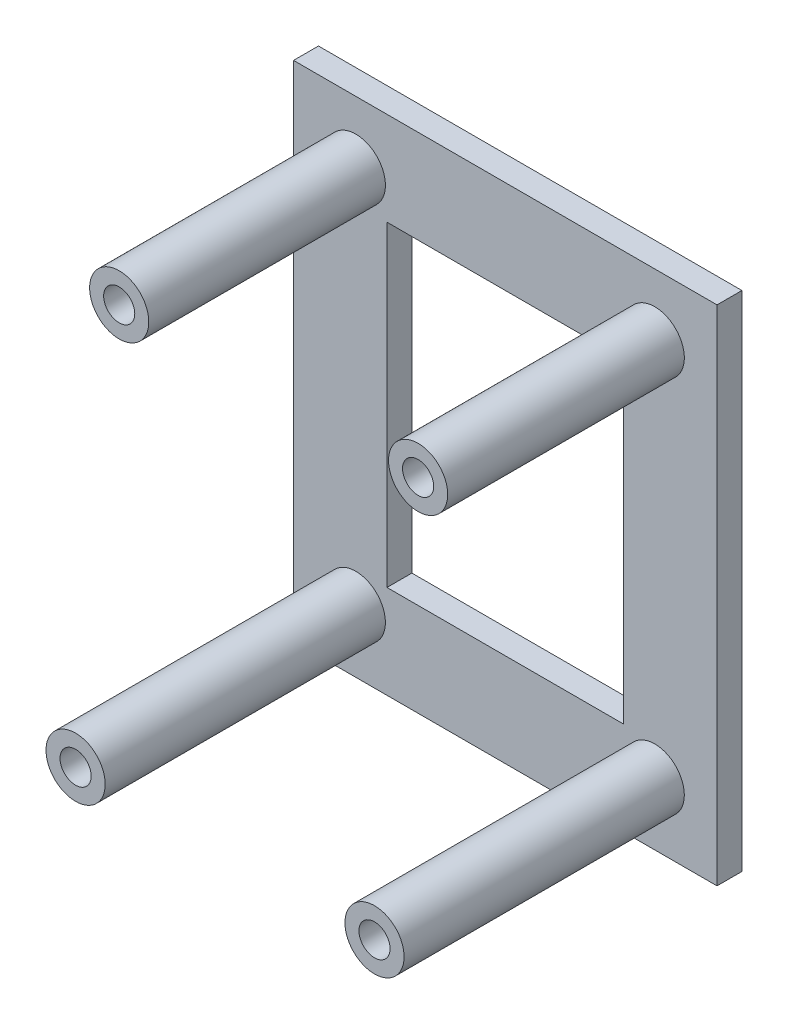
SolidWorks part; units mm, degrees
ref_plane "Front Plane" through (0, 0, 0) normal (0, 0, 1) x (1, 0, 0)
ref_plane "Top Plane" through (0, 0, 0) normal (0, 1, 0) x (1, 0, 0)
ref_plane "Right Plane" through (0, 0, 0) normal (1, 0, 0) x (0, 0, -1)
sketch "Sketch1" plane through (0, 0, 0) normal (0, 0, 1) x (1, 0, 0)
  line L0 (0, -15.2) -> (0, -20.2) construction
  line L1 (-5, 20.2) -> (29, 20.2)
  line L2 (-5, 20.2) -> (-5, -20.2)
  line L3 (-5, -20.2) -> (29, -20.2)
  line L4 (29, 20.2) -> (29, -20.2)
  line L5 (2.5, 12.7) -> (21.5, 12.7)
  line L6 (2.5, 12.7) -> (2.5, -12.7)
  line L7 (2.5, -12.7) -> (21.5, -12.7)
  line L8 (21.5, 12.7) -> (21.5, -12.7)
  line L9 (0, 15.2) -> (0, 20.2) construction
  line L10 (0, 15.2) -> (0, 12.7) construction
  line L11 (0, -15.2) -> (0, -12.7) construction
  circle A0 centre (0, -15.2) radius 1.25
  circle A1 centre (24, -15.2) radius 1.25
  circle A2 centre (24, 15.2) radius 1.25
  circle A3 centre (0, 15.2) radius 1.25
  circle A4 centre (0, 15.2) radius 2.375
  circle A5 centre (24, 15.2) radius 2.375
  circle A6 centre (24, -15.2) radius 2.375
  circle A7 centre (0, -15.2) radius 2.375
  dimension "D3" = 2.5
  dimension "D5" = 24
  dimension "D6" = 5
  dimension "D4" = 15.2
  dimension "D12" = 4.75
  dimension "D1" = 30.4
  dimension "D2" = 24
  dimension "D7" = 5
  dimension "D8" = 5
  dimension "D9" = 2.5
  dimension "D10" = 2.5
  dimension "D11" = 2.5
extrude "Boss-Extrude1" add sketch "Sketch1" along normal blind 2 contours L8 L5 L6 L7 | L1 L4 L3 L2 region at (12, 0, 0)
extrude "Boss-Extrude2" add sketch "Sketch1<3>" along normal blind 21 contours A5 | A4
sketch "Sketch1<3>" plane through (0, 0, 0) normal (0, 0, 1) x (1, 0, 0) same geometry as "Sketch1"
extrude "Cut-Extrude1" cut sketch "Sketch1<4>" against normal blind 15 from surface contours A3 | A2 region at (24, 15.2, 0) region at (0, 15.2, 0) starting at face at (2.375, 15.2, 21)
sketch "Sketch1<4>" plane through (0, 0, 0) normal (0, 0, 1) x (1, 0, 0) same geometry as "Sketch1"
extrude "Boss-Extrude3" add sketch "Sketch1<6>" along normal blind 24.5 contours A6 | A7
sketch "Sketch1<6>" plane through (0, 0, 0) normal (0, 0, 1) x (1, 0, 0) same geometry as "Sketch1"
extrude "Cut-Extrude2" cut sketch "Sketch1<8>" against normal blind 18.5 from surface contours A0 | A1 starting at face at (2.375, -15.2, 24.5)
sketch "Sketch1<8>" plane through (0, 0, 0) normal (0, 0, 1) x (1, 0, 0) same geometry as "Sketch1"
